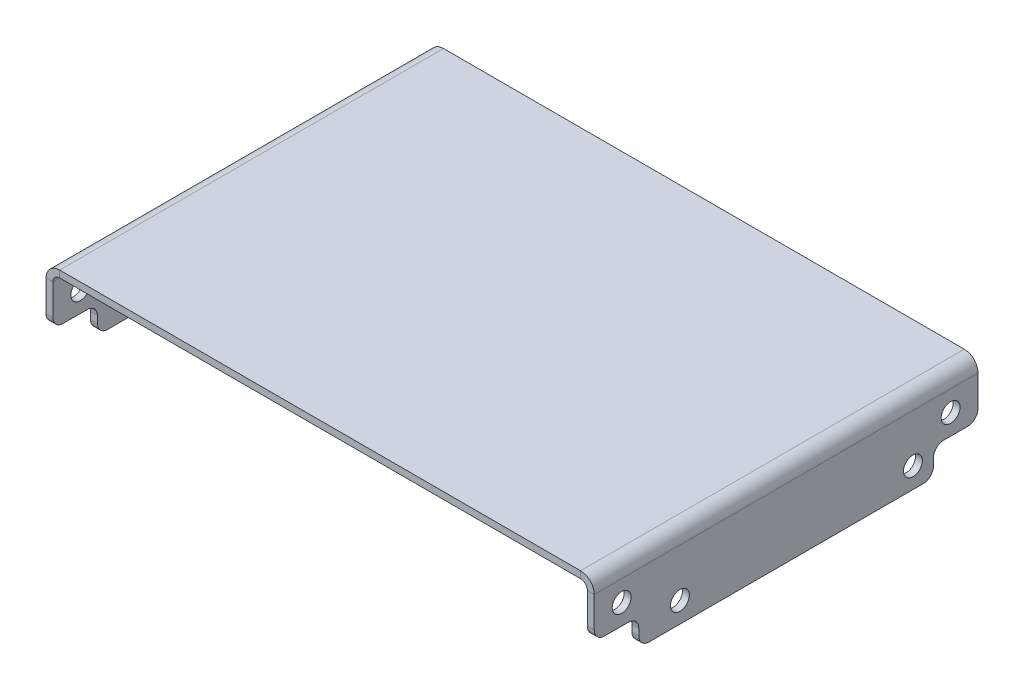
SolidWorks part; units mm, degrees
note: The reader was unsure of these and kept them because the rebuilt part matched: thickness of "Base-Flange1", "Edge-Flange1", "Sheet-Metal1", "Sheet-Metal2", "Sheet-Metal5", "Sheet-Metal8", "Sheet-Metal9"; flange length of "Edge-Flange1".
material "5052-H32"
ref_plane "Front Plane" through (0, 0, 0) normal (0, 0, 1) x (1, 0, 0)
ref_plane "Top Plane" through (0, 0, 0) normal (0, 1, 0) x (1, 0, 0)
ref_plane "Right Plane" through (0, 0, 0) normal (1, 0, 0) x (0, 0, -1)
sketch "Sketch1" plane through (0, 0, 0) normal (0, 1, 0) x (1, 0, 0)
  line L1 (120.65, 88.9) -> (-120.65, 88.9)
  line L2 (120.65, 88.9) -> (120.65, -88.9)
  line L3 (120.65, -88.9) -> (-120.65, -88.9)
  line L4 (-120.65, 88.9) -> (-120.65, -88.9)
  line L5 (120.65, 88.9) -> (-120.65, -88.9) construction
  line L6 (120.65, -88.9) -> (-120.65, 88.9) construction
  point P0 (0, 0)
  dimension "D1" = 177.8
  dimension "D2" = 241.3
base flange "Base-Flange1" sketch "Sketch1" thickness 3.175 reverse thickness direction no parameters "D1"=3.175
edge flange "Edge-Flange1" sketch "Sketch32" flange profiles "Sketch32", "Sketch34" flange angle 90 flange length 25.4 flange position bend outside bend radius 3.175 thickness 3.175 relief rectangular parameters "D1"=3.9688, "D6"=10, "D8"=1
bend "EdgeBend7" bend radius 3.175 bend angle 90 parameters "D5"=1
bend "EdgeBend8" bend radius 3.175 bend angle 90 parameters "D5"=2
sketch "Sketch32" plane through (120.65, -3.175, 0) normal (-1, 0, 0) x (0, 0, -1)
  line L0 (88.9, 0) -> (-88.9, 0) construction
  line L1 (88.9, 0) -> (-88.9, 0)
  line L2 (88.9, 0) -> (88.9, 22.225)
  line L3 (88.9, 22.225) -> (-88.9, 22.225)
  line L4 (-88.9, 22.225) -> (-88.9, 0)
sketch "Sketch34" plane through (-120.65, -3.175, 0) normal (1, 0, 0) x (0, 0, 1)
  line L0 (88.9, 0) -> (-88.9, 0) construction
  line L1 (88.9, 0) -> (-88.9, 0)
  line L2 (88.9, 0) -> (88.9, 22.225)
  line L3 (88.9, 22.225) -> (-88.9, 22.225)
  line L4 (-88.9, 22.225) -> (-88.9, 0)
sketch "Sketch13" plane through (127, 0, 0) normal (1, 0, 0) x (0, 0, -1)
  line L0 (88.9, -25.4) -> (-88.9, -25.4) construction
  line L1 (-68.2625, -25.4) -> (68.2625, -25.4)
  line L2 (-68.2625, -25.4) -> (-68.2625, -38.1)
  line L3 (-68.2625, -38.1) -> (68.2625, -38.1)
  line L4 (68.2625, -25.4) -> (68.2625, -38.1)
  line L8 (-88.9, -25.4) -> (-88.9, -6.35) construction
  line L9 (-88.9, 0) -> (88.9, 0) construction
  circle A0 centre (-49.2125, -28.575) radius 7.9375 construction
  circle A1 centre (58.7375, -28.575) radius 7.9375 construction
  circle A2 centre (-76.2, -15.875) radius 7.9375 construction
  circle A3 centre (76.2, -15.875) radius 7.9375 construction
  circle A4 centre (-49.2125, -28.575) radius 12.7 construction
  circle A5 centre (58.7375, -28.575) radius 12.7 construction
  point P0 (-49.2125, -28.575)
  point P1 (58.7375, -28.575)
  point P22 (0, -38.1)
  dimension "D4" = 15.875
  dimension "D8" = 25.4
  dimension "D1" = 15.875
  dimension "D2" = 12.7
  dimension "D3" = 107.95
  dimension "D5" = 28.575
  dimension "D6" = 152.4
  dimension "D7" = 39.6875
  dimension "D9" = 38.1
  dimension "D10" = 136.525
extrude "Boss-Extrude1" add sketch "Sketch13" against normal up to surface (3.175 mm away) up to face at (123.825, -15.875, 0)
sketch "Sketch39" plane through (-127, 0, 0) normal (-1, 0, 0) x (0, 0, 1)
  line L4 (68.2625, -25.4) -> (-68.2625, -25.4)
  line L5 (68.2625, -38.1) -> (68.2625, -25.4)
  line L6 (-68.2625, -38.1) -> (68.2625, -38.1)
  line L7 (-68.2625, -25.4) -> (-68.2625, -38.1)
  line L8 (68.2625, -25.4) -> (-68.2625, -25.4)
  line L9 (68.2625, -38.1) -> (68.2625, -25.4)
  line L10 (-68.2625, -38.1) -> (68.2625, -38.1)
  line L11 (-68.2625, -25.4) -> (-68.2625, -38.1)
  dimension "D1" = 0
extrude "Boss-Extrude2" add sketch "Sketch39" against normal up to surface (3.175 mm away) up to face at (-123.825, -15.875, 0)
hole_wizard "Hole for 1/4 Self-clinching Nuts (S,SS,CLS,CLSS)1" positions "Sketch20" profile "Sketch21" hole size "1/4-20" standard "PEM® Inch" end condition through all
sketch "Sketch20" plane through (127, 0, 0) normal (1, 0, 0) x (0, 0, -1)
  point P0 (-76.2, -15.875)
  point P3 (76.2, -15.875)
  point P6 (58.7375, -28.575)
  point P8 (-49.2125, -28.575)
sketch "Sketch21" plane through (127, -15.875, 76.2) normal (0, 1, 0) x (0, 0, -1)
  line L0 (0, 0) -> (0, 254)
  line L1 (0, 254) -> (4.3688, 254)
  line L2 (4.3688, 254) -> (4.3688, 0)
  line L5 (4.3688, 0) -> (0, 0)
  line L11 (0, -6.35) -> (0, 107.95) construction
  dimension "Thru Hole Dia." = 8.7376
  dimension "Thru Hole Depth" = 254
fillet "Fillet2" radius 4.7625 12 edges at (-125.4125, -25.4, 88.9) (125.4125, -25.4, 88.9) (-125.4125, -25.4, -88.9) (125.4125, -25.4, -88.9) (-125.4125, -25.4, -68.2625) (125.4125, -25.4, -68.2625) (125.4125, -38.1, -68.2625) (125.4125, -38.1, 68.2625) (125.4125, -25.4, 68.2625) (-125.4125, -38.1, -68.2625) (-125.4125, -38.1, 68.2625) (-125.4125, -25.4, 68.2625)
sketch "Bend-Lines1" [suppressed] plane through (0, 0, 0) normal (0, 1, 0) x (1, 0, 0)
sketch "Bounding-Box1" [suppressed] plane through (0, 0, 0) normal (0, 1, 0) x (1, 0, 0)
sheet metal parameters "Sheet-Metal1" thickness 3.175 parameters "D1"=1.27, "D7"=1.9844
flat pattern "Flat-Pattern1" [suppressed]
sketch "Bend-Lines2" plane through (0, 0, 0) normal (0, 1, 0) x (1, 0, 0)
sketch3d "Bounding-Box2" [suppressed]
  line L0 (127, 82.55, 0) -> (-127, 82.55, 0) construction
  line L1 (127, -82.55, 0) -> (-127, -82.55, 0) construction
  line L2 (127, 82.55, 0) -> (127, -82.55, 0) construction
  line L3 (-127, 82.55, 0) -> (-127, -82.55, 0) construction
sheet metal parameters "Sheet-Metal2" thickness 3.175 parameters "D1"=1.27, "D7"=1.9844
flat pattern "Flat-Pattern1"
sketch "Bend-Lines2" plane through (0, 0, 0) normal (0, 1, 0) x (1, 0, 0)
  line L4 (-124.3673, 82.55) -> (-124.3673, -82.55) construction
  line L5 (124.3673, -82.55) -> (124.3673, 82.55) construction
  line L6 (-124.3673, 82.55) -> (-124.3673, -82.55) construction
  line L7 (124.3673, -82.55) -> (124.3673, 82.55) construction
  point P1 (-119.38, -87.5373)
  point P2 (119.38, -87.5373)
  point P6 (119.38, 87.5373)
  point P7 (-119.38, 87.5373)
sketch3d "Bounding-Box2" [suppressed]
  line L0 (147.1346, 82.55, 0) -> (-147.1346, 82.55, 0) construction
  line L1 (147.1346, -82.55, 0) -> (-147.1346, -82.55, 0) construction
  line L2 (147.1346, 82.55, 0) -> (147.1346, -82.55, 0) construction
  line L3 (-147.1346, 82.55, 0) -> (-147.1346, -82.55, 0) construction
bend of the flat pattern "Flatten-<EdgeBend7>1"
bend of the flat pattern "Flatten-<EdgeBend8>1"
sheet metal parameters "Sheet-Metal5" thickness 3.175 parameters "D1"=1.27, "D7"=1.9844
flat pattern "Flat-Pattern1" [suppressed]
sketch "Bend-Lines2" plane through (0, 0, 0) normal (0, 1, 0) x (1, 0, 0)
  line L0 (-124.3905, 88.9) -> (-124.3905, -88.9) construction
  line L1 (124.3905, -88.9) -> (124.3905, 88.9) construction
  line L2 (-124.3905, 88.9) -> (-124.3905, -88.9) construction
  line L3 (124.3905, -88.9) -> (124.3905, 88.9) construction
sketch3d "Bounding-Box2" [suppressed]
  line L0 (-159.8809, 88.8998, 0) -> (159.8809, 88.9, 0) construction
  line L1 (-159.8808, -88.9, 0) -> (159.881, -88.8998, 0) construction
  line L2 (-159.8809, 88.8998, 0) -> (-159.8808, -88.9, 0) construction
  line L3 (159.8809, 88.9, 0) -> (159.881, -88.8998, 0) construction
bend of the flat pattern "Flatten-<EdgeBend8>2"
bend of the flat pattern "Flatten-<EdgeBend7>2"
sketch "Sketch13-1" plane through (121.7809, 0, 0) normal (0, 1, 0) x (0, 0, -1)
  line L1 (-68.2625, -25.4) -> (68.2625, -25.4)
  line L2 (-68.2625, -25.4) -> (-68.2625, -38.1)
  line L3 (-68.2625, -38.1) -> (68.2625, -38.1)
  line L4 (68.2625, -25.4) -> (68.2625, -38.1)
  line L8 (-88.9, -20.6375) -> (-88.9, 264.1993) construction
  line L9 (-88.9, 0) -> (88.9, 0) construction
  circle A0 centre (-49.2125, -28.575) radius 7.9375 construction
  circle A1 centre (58.7375, -28.575) radius 7.9375 construction
  circle A2 centre (-76.2, -15.875) radius 7.9375 construction
  circle A3 centre (76.2, -15.875) radius 7.9375 construction
  circle A4 centre (-49.2125, -28.575) radius 12.7 construction
  circle A5 centre (58.7375, -28.575) radius 12.7 construction
  point P0 (-49.2125, -28.575)
  point P1 (58.7375, -28.575)
  dimension "D4" = 15.875
  dimension "D8" = 25.4
  dimension "D1" = 15.875
  dimension "D2" = 12.7
  dimension "D3" = 107.95
  dimension "D5" = 28.575
  dimension "D6" = 152.4
  dimension "D7" = 39.6875
  dimension "D9" = 38.1
  dimension "D10" = 136.525
sheet metal parameters "Sheet-Metal8" thickness 3.175 parameters "D1"=1.27, "D7"=1.9844
flat pattern "Flat-Pattern1"
sketch "Bend-Lines2" plane through (0, 0, 0) normal (0, 1, 0) x (1, 0, 0)
  line L4 (-124.3905, 88.9) -> (-124.3905, -88.9) construction
  line L5 (124.3905, -88.9) -> (124.3905, 88.9) construction
  line L6 (-124.3905, 88.9) -> (-124.3905, -88.9) construction
  line L7 (124.3905, -88.9) -> (124.3905, 88.9) construction
sketch3d "Bounding-Box2" [suppressed]
  line L0 (166.2309, 88.9, 0) -> (-147.1809, 88.9, 0) construction
  line L1 (166.2309, -88.9, 0) -> (-147.1809, -88.9, 0) construction
  line L2 (166.2309, 88.9, 0) -> (166.2309, -88.9, 0) construction
  line L3 (-147.1809, 88.9, 0) -> (-147.1809, -88.9, 0) construction
bend of the flat pattern "Flatten-<EdgeBend7>1"
bend of the flat pattern "Flatten-<EdgeBend8>1"
sheet metal parameters "Sheet-Metal9" thickness 3.175 parameters "D1"=1.27, "D7"=1.9844
flat pattern "Flat-Pattern1"
sketch "Bend-Lines2" plane through (0, 0, 0) normal (0, 1, 0) x (1, 0, 0)
  line L4 (-124.3905, 88.9) -> (-124.3905, -88.9) construction
  line L5 (124.3905, -88.9) -> (124.3905, 88.9) construction
  line L6 (-124.3905, 88.9) -> (-124.3905, -88.9) construction
  line L7 (124.3905, -88.9) -> (124.3905, 88.9) construction
sketch3d "Bounding-Box2" [suppressed]
  line L0 (166.2309, 88.9, 0) -> (-166.2309, 88.9, 0) construction
  line L1 (166.2309, -88.9, 0) -> (-166.2309, -88.9, 0) construction
  line L2 (166.2309, 88.9, 0) -> (166.2309, -88.9, 0) construction
  line L3 (-166.2309, 88.9, 0) -> (-166.2309, -88.9, 0) construction
bend of the flat pattern "Flatten-<EdgeBend7>1"
bend of the flat pattern "Flatten-<EdgeBend8>1"
